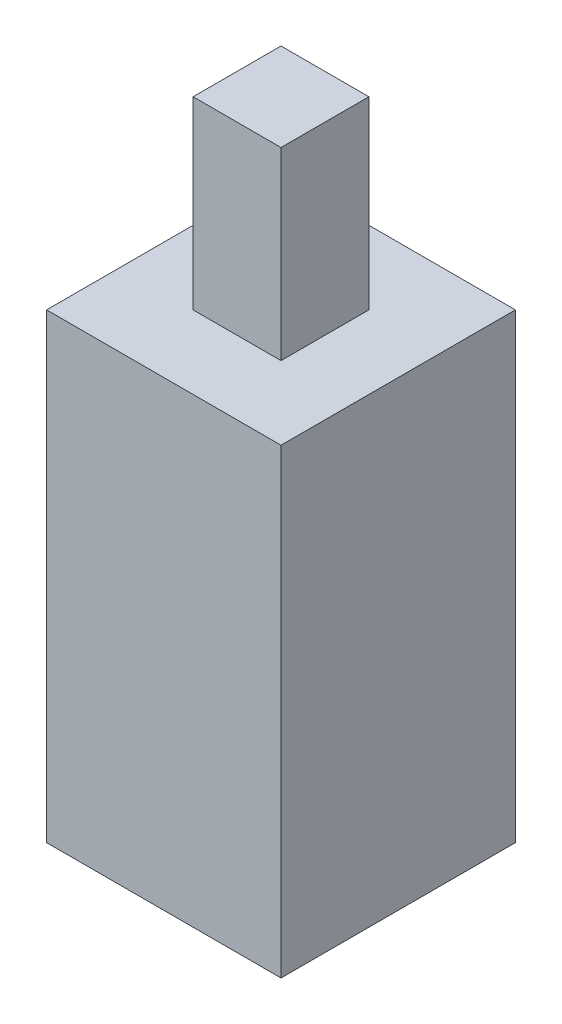
SolidWorks part; units mm, degrees
ref_plane "Front Plane" through (0, 0, 0) normal (0, 0, 1) x (1, 0, 0)
ref_plane "Top Plane" through (0, 0, 0) normal (0, 1, 0) x (1, 0, 0)
ref_plane "Right Plane" through (0, 0, 0) normal (1, 0, 0) x (0, 0, -1)
sketch "Sketch1" plane through (0, 0, 0) normal (0, 1, 0) x (1, 0, 0)
  line L1 (0, 0) -> (10.16, 0)
  line L2 (0, 0) -> (0, 10.16)
  line L3 (0, 10.16) -> (10.16, 10.16)
  line L4 (10.16, 0) -> (10.16, 10.16)
  dimension "D1" = 10.16
  dimension "D2" = 10.16
extrude "Boss-Extrude1" add sketch "Sketch1" along normal blind 20
sketch "Sketch2" plane through (0, 20, 0) normal (0, 1, 0) x (1, 0, 0)
  line L6 (0, 10.16) -> (0, 0) construction
  line L7 (6.985, 3.175) -> (3.175, 3.175)
  line L8 (6.985, 3.175) -> (6.985, 6.985)
  line L9 (6.985, 6.985) -> (3.175, 6.985)
  line L10 (3.175, 3.175) -> (3.175, 6.985)
  line L11 (6.985, 3.175) -> (3.175, 6.985) construction
  line L12 (6.985, 6.985) -> (3.175, 3.175) construction
  line L13 (0, 0) -> (10.16, 0) construction
  point P0 (5.08, 5.08)
  dimension "D1" = 5.08
  dimension "D2" = 5.08
  dimension "D3" = 3.81
  dimension "D4" = 3.81
extrude "Boss-Extrude2" add sketch "Sketch2" along normal blind 8
sketch "Sketch3" plane through (0, 0, 0) normal (0, -1, 0) x (-1, 0, 0)
  line L0 (0, 0) -> (-10.16, 0) construction
  line L1 (-8.08, 8.08) -> (-2.08, 8.08)
  line L2 (-8.08, 8.08) -> (-8.08, 2.08)
  line L3 (-8.08, 2.08) -> (-2.08, 2.08)
  line L4 (-2.08, 8.08) -> (-2.08, 2.08)
  line L5 (-8.08, 8.08) -> (-2.08, 2.08) construction
  line L6 (-8.08, 2.08) -> (-2.08, 8.08) construction
  line L7 (0, 10.16) -> (0, 0) construction
  point P0 (-5.08, 5.08)
  point P7 (0, 0)
  dimension "D1" = 5.08
  dimension "D2" = 5.08
  dimension "D3" = 6
  dimension "D4" = 6
extrude "Cut-Extrude1" cut sketch "Sketch3" against normal blind 2
